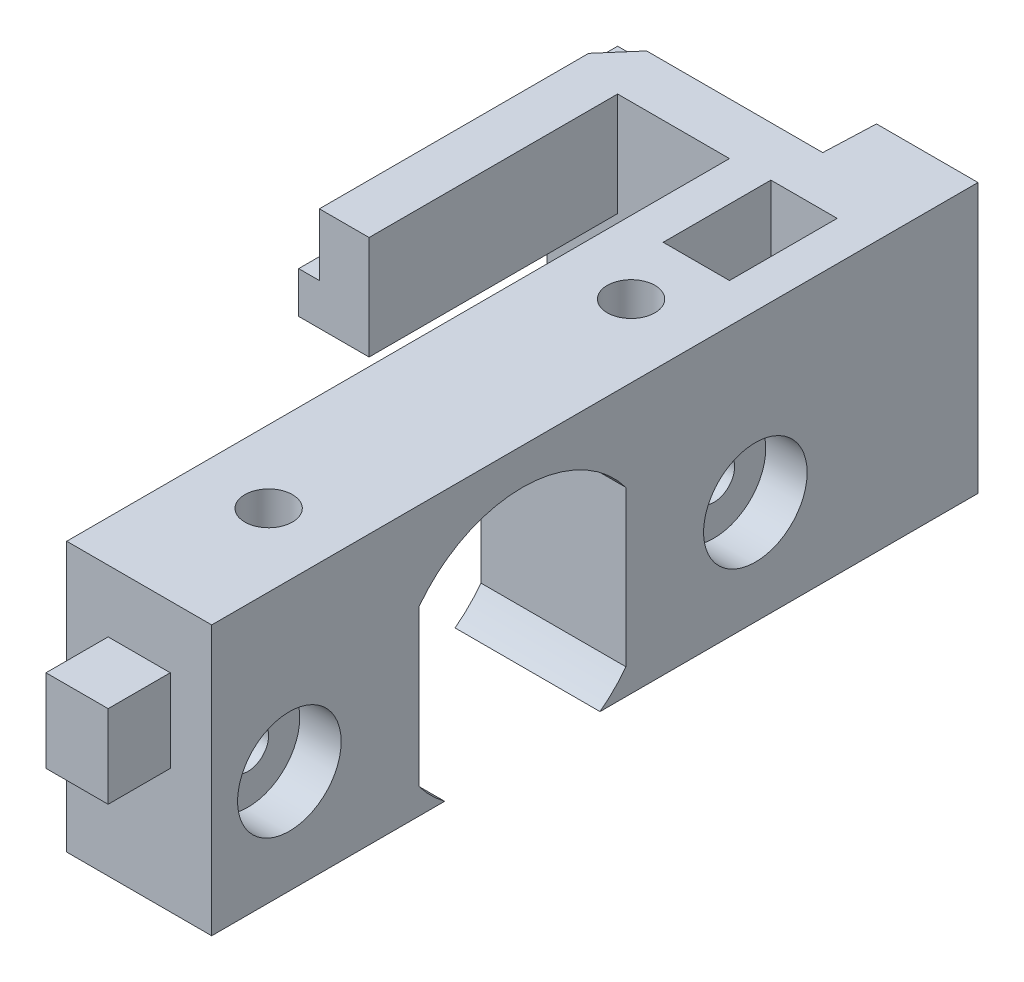
SolidWorks part; units mm, degrees
ref_plane "Front Plane" through (0, 0, 0) normal (0, 0, 1) x (1, 0, 0)
ref_plane "Top Plane" through (0, 0, 0) normal (0, 1, 0) x (1, 0, 0)
ref_plane "Right Plane" through (0, 0, 0) normal (1, 0, 0) x (0, 0, -1)
sketch "Sketch2" plane through (0, 0, 0) normal (1, 0, 0) x (0, 0, -1)
  line L0 (-11.25, 0) -> (11.25, 0) construction
  line L5 (3.75, -5) -> (15, -5)
  line L7 (-15, -5) -> (-3.75, -5)
  line L8 (-15, -5) -> (-15, 8)
  line L9 (-15, 8) -> (15, 8)
  line L10 (15, -5) -> (15, 8)
  line L11 (-21.1921, -10.5) -> (21.1921, -10.5)
  line L12 (-26.7679, -7) -> (23.2321, -7) construction
  line L13 (-26.7679, -7) -> (-26.7679, -5) construction
  line L14 (-26.7679, -5) -> (-3.75, -5) construction
  line L15 (23.2321, -7) -> (23.2321, -5) construction
  line L16 (-26.7679, -7) -> (23.2321, -5) construction
  line L17 (-26.7679, -5) -> (23.2321, -7) construction
  line L18 (-5, -3.75) -> (-5, 3.75)
  line L19 (8.75, -3) -> (13.75, -3) construction
  line L20 (8.75, -3) -> (8.75, 3) construction
  line L21 (8.75, 3) -> (13.75, 3) construction
  line L22 (13.75, -3) -> (13.75, 3) construction
  line L23 (8.75, -3) -> (13.75, 3) construction
  line L24 (8.75, 3) -> (13.75, -3) construction
  line L26 (5, -3.75) -> (5, 3.75)
  line L27 (-5, -3.75) -> (5, 3.75) construction
  line L28 (-5, 3.75) -> (5, -3.75) construction
  line L29 (3.75, -5) -> (23.2321, -5) construction
  circle A2 centre (0, 0) radius 1.75 construction
  circle A3 centre (11.25, 0) radius 9.5 construction
  circle A4 centre (-11.25, 0) radius 9.5 construction
  circle A5 centre (11.25, 0) radius 10.5 construction
  circle A6 centre (-11.25, 0) radius 10.5 construction
  circle A7 centre (0, 0) radius 0.5
  circle A8 centre (-11.25, 0) radius 1
  circle A9 centre (11.25, 0) radius 1
  arc A10 (5, 3.75) -> (-5, 3.75) centre (0, 0) ccw
  arc A11 (-5, -3.75) -> (-3.75, -5) centre (0, 0) ccw
  arc A13 (3.75, -5) -> (5, -3.75) centre (0, 0) ccw
  point P14 (0, 0)
  point P18 (0, 8)
  point P19 (-1.7679, -6)
  point P30 (0, -10.5)
  dimension "D3" = 3.5
  dimension "D4" = 19
  dimension "D5" = 21
  dimension "D6" = 30
  dimension "D10" = 1
  dimension "D11" = 2
  dimension "D2" = 12.5
  dimension "D7" = 13
  dimension "D8" = 2
  dimension "D9" = 50
  dimension "D12" = 5
  dimension "D13" = 6
  dimension "D14" = 10
extrude "Boss-Extrude1" add sketch "Sketch2" along normal blind 7 contours L7 L10 L9 L8 A9 A8 region at (0, -4.6506, -4.6506)
sketch "Sketch3" plane through (0, 0, 0) normal (0, 1, 0) x (1, 0, 0)
  line L0 (0, 3.75) -> (0, 15) construction
  line L1 (7, 3.75) -> (0, 3.75) construction
  line L2 (7, -3.75) -> (0, -3.75) construction
  circle A0 centre (3.5, 8.75) radius 1.15
  circle A1 centre (3.5, -8.75) radius 1.15
  dimension "D1" = 2.3
  dimension "D2" = 3.5
  dimension "D3" = 5
  dimension "D4" = 5
extrude "Cut-Extrude1" cut sketch "Sketch3" along normal blind 13 from surface starting at face at (3.5, -5, -9.375)
sketch "Sketch5" plane through (0, 0, 0) normal (1, 0, 0) x (0, 0, -1)
  circle A0 centre (11.25, 0) radius 2.5
  circle A1 centre (-11.25, 0) radius 2.5
  dimension "D1" = 5
extrude "Cut-Extrude2" cut sketch "Sketch5" along normal blind 2
extrude "Cut-Extrude3" cut sketch "Sketch5<2>" against normal blind 2 from surface starting at face at (7, -0.1589, 0)
sketch "Sketch5<2>" plane through (0, 0, 0) normal (1, 0, 0) x (0, 0, -1) same geometry as "Sketch5"
sketch "Sketch6" plane through (0, 0, 0) normal (0, 1, 0) x (1, 0, 0)
  line L2 (7, 15) -> (7, 25)
  line L3 (7, 25) -> (-10.4, 25)
  line L6 (-10.4, 25) -> (-10.4, 5)
  line L7 (-10.4, 5) -> (-5.4, 5)
  line L8 (-5.4, 22) -> (-5.4, 5)
  line L9 (0, -15) -> (0, 15) construction
  line L10 (7, 15) -> (0, 15)
  line L11 (0, 15) -> (0, 22)
  line L12 (0, 22) -> (-5.4, 22)
  dimension "D1" = 10
  dimension "D2" = 10.4
  dimension "D3" = 5
  dimension "D4" = 3
  dimension "D5" = 20
extrude "Boss-Extrude2" add sketch "Sketch6" along normal blind 13 from surface starting at face at (3.5, -5, -7.6)
sketch "Sketch7" plane through (0, 0, 0) normal (1, 0, 0) x (0, 0, -1)
  line L0 (5, 8) -> (5, -5) construction
  line L1 (5, 3) -> (17, 3)
  line L2 (5, 3) -> (5, -3)
  line L3 (5, -3) -> (17, -3)
  line L4 (17, 3) -> (17, -3)
  line L5 (25, -5) -> (5, -5) construction
  dimension "D1" = 6
  dimension "D2" = 2
  dimension "D3" = 12
extrude "Cut-Extrude4" cut sketch "Sketch7" against normal blind 5 from surface starting at face at (-5.4, 1.5, -13.5)
sketch "Sketch8" plane through (0, 0, 0) normal (1, 0, 0) x (0, 0, -1)
  line L0 (25, -5) -> (5, -5) construction
  line L1 (5, 8) -> (20, 8)
  line L2 (5, 8) -> (5, -5)
  line L3 (5, -5) -> (20, -5)
  line L4 (20, 8) -> (20, -5)
  dimension "D1" = 15
extrude "Cut-Extrude5" cut sketch "Sketch8" along normal blind 1.6 from surface starting at face at (-10.4, 0.75, -13)
sketch "Sketch9" plane through (0, 0, 0) normal (1, 0, 0) x (0, 0, -1)
  line L1 (5, 8) -> (18, 8)
  line L2 (5, 8) -> (5, 5)
  line L3 (5, 5) -> (18, 5)
  line L4 (18, 8) -> (18, 5)
  dimension "D1" = 13
  dimension "D2" = 3
extrude "Cut-Extrude6" cut sketch "Sketch9" along normal blind 1 from surface starting at face at (-8.8, 0.75, -11.75)
sketch "Sketch10" plane through (0, 0, 0) normal (0, 1, 0) x (1, 0, 0)
  line L0 (0, -15) -> (0, 22) construction
  line L1 (-5.4, 22) -> (0, 22)
  line L2 (-5.4, 22) -> (-5.4, 17)
  line L3 (-5.4, 17) -> (0, 17)
  line L4 (0, 22) -> (0, 17)
  dimension "D1" = 5
extrude "Boss-Extrude4" add sketch "Sketch10" against normal up to surface (5 mm away) from surface up to face at (3.5, -5, -7.6) starting at face at (3.5, 8, -7.6)
sketch "Sketch11" plane through (0, 0, 0) normal (0, 1, 0) x (1, 0, 0)
  line L0 (-10.4, 25) -> (-10.4, 20) construction
  line L1 (7, 25) -> (-10.4, 25)
  line L2 (7, 25) -> (7, 22)
  line L3 (7, 22) -> (-10.4, 22)
  line L4 (-10.4, 25) -> (-10.4, 22)
  dimension "D1" = 3
extrude "Cut-Extrude7" cut sketch "Sketch11" against normal up to surface (5 mm away) from surface up to face at (-3.52, -5, -14.15) starting at face at (-4.2333, 8, -11.6667)
sketch "Sketch12" plane through (0, 0, 0) normal (0, 0, 1) x (1, 0, 0)
  line L0 (7, -5) -> (7, 8) construction
  line L1 (2, 5) -> (5, 5)
  line L2 (2, 5) -> (2, 1)
  line L3 (2, 1) -> (5, 1)
  line L4 (5, 5) -> (5, 1)
  line L5 (2, 5) -> (5, 1) construction
  line L6 (2, 1) -> (5, 5) construction
  line L7 (7, -5) -> (0, -5) construction
  point P0 (3.5, 3)
  dimension "D1" = 4
  dimension "D2" = 3
  dimension "D3" = 2
  dimension "D4" = 6
extrude "Boss-Extrude5" add sketch "Sketch12" along normal blind 3 from surface starting at face at (3.5, 1.5, 15)
sketch "Sketch13" plane through (0, 0, 0) normal (0, 1, 0) x (1, 0, 0)
  line L0 (2.1, 22) -> (2.0001, 19.502)
  line L2 (2.0001, 19.502) -> (-6.4999, 19.502)
  line L3 (-6.4999, 19.502) -> (-7.9, 22)
  line L4 (7, 22) -> (-10.4, 22) construction
  line L5 (-7.9, 22) -> (2.1, 22)
  dimension "D1" = 2.5
  dimension "D2" = 8.5
  dimension "D3" = 10
  dimension "D4" = 2.5
extrude "Cut-Extrude8" cut sketch "Sketch13" against normal up to surface (5 mm away) from surface up to face at (3.5, -5, -7.6) starting at face at (3.5, 8, -7.6)
sketch "Sketch14" plane through (0, 0, 0) normal (0, 1, 0) x (1, 0, 0)
  line L0 (-6.4999, 19.502) -> (-7.8, 18)
  line L1 (-7.8, 18) -> (-8.8, 18)
  line L2 (-8.8, 18) -> (-8.8, 20)
  line L3 (-8.8, 20) -> (-10.4, 20)
  line L4 (-10.4, 20) -> (-10.4, 22)
  line L5 (-10.4, 22) -> (-7.9, 22)
  line L6 (-7.9, 22) -> (-10.4, 22) construction
  line L7 (-6.4999, 19.502) -> (-7.9, 22) construction
  line L8 (-7.9, 22) -> (-6.4999, 19.502)
extrude "Cut-Extrude9" cut sketch "Sketch14" against normal blind 3 from surface starting at face at (3.5, 8, -7.6)
sketch "Sketch15" plane through (0, 0, 0) normal (0, 1, 0) x (1, 0, 0)
  line L0 (0, -15) -> (0, 17) construction
  line L1 (1.9, 17.1) -> (5.1, 17.1)
  line L2 (1.9, 17.1) -> (1.9, 11.9)
  line L3 (1.9, 11.9) -> (5.1, 11.9)
  line L4 (5.1, 17.1) -> (5.1, 11.9)
  line L5 (1.9, 17.1) -> (5.1, 11.9) construction
  line L6 (1.9, 11.9) -> (5.1, 17.1) construction
  line L7 (7, 22) -> (2.1, 22) construction
  point P0 (3.5, 14.5)
  dimension "D1" = 3.2
  dimension "D2" = 1.9
  dimension "D3" = 4.9
  dimension "D4" = 5.2
extrude "Cut-Extrude10" cut sketch "Sketch15" against normal blind 3.2 from surface starting at face at (3.5, 8, -7.6)
